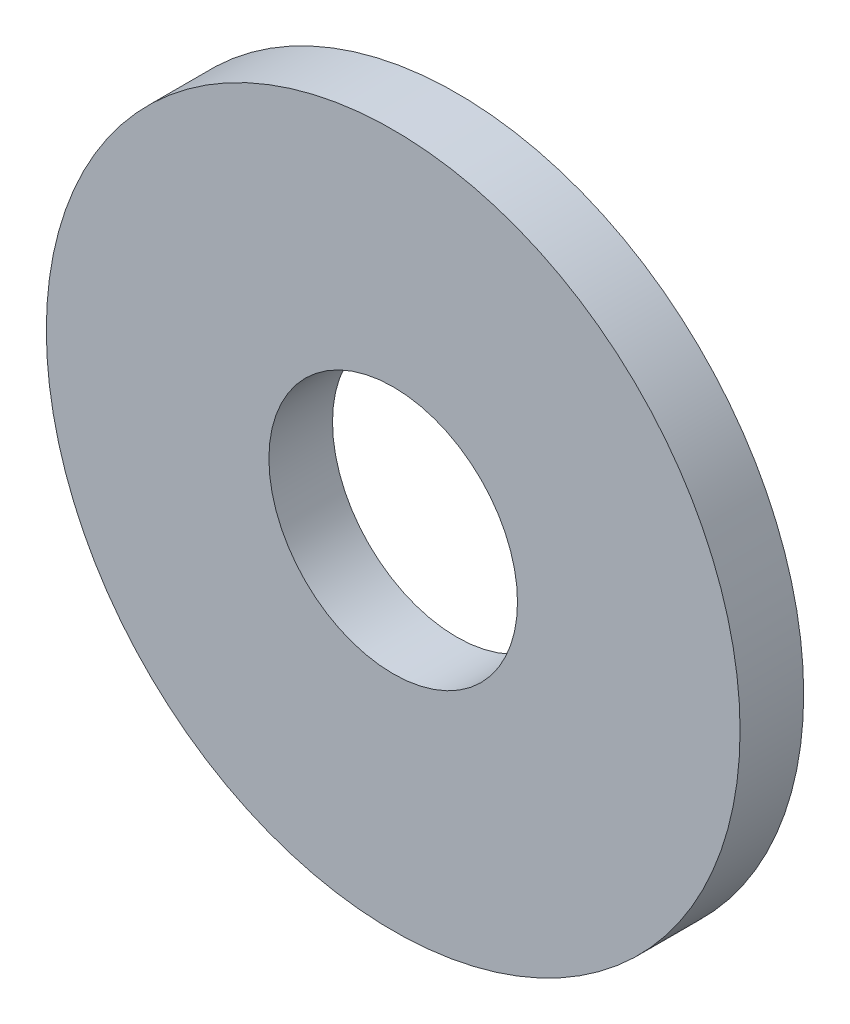
SolidWorks part; units mm, degrees
material "Alloy Steel"
ref_plane "Front Plane" through (0, 0, 0) normal (0, 0, 1) x (1, 0, 0)
ref_plane "Top Plane" through (0, 0, 0) normal (0, 1, 0) x (1, 0, 0)
ref_plane "Right Plane" through (0, 0, 0) normal (1, 0, 0) x (0, 0, -1)
ref_axis "Axis1" through (0, 0, -12.737) along (0, 0, 1)
ref_axis "Axis2" through (0, -40.0342, 0) along (0, 1, 0)
ref_axis "Axis3" through (-41.1327, 0, 0) along (1, 0, 0)
sketch "Sketch1" plane through (0, 0, 0) normal (0, 0, 1) x (1, 0, 0)
  circle A0 centre (0, 0) radius 6
  circle A1 centre (0, 0) radius 2.15
  dimension "OD" = 12
  dimension "ID" = 4.3
extrude "Boss-Extrude1" add sketch "Sketch1" along normal mid plane 1.1
